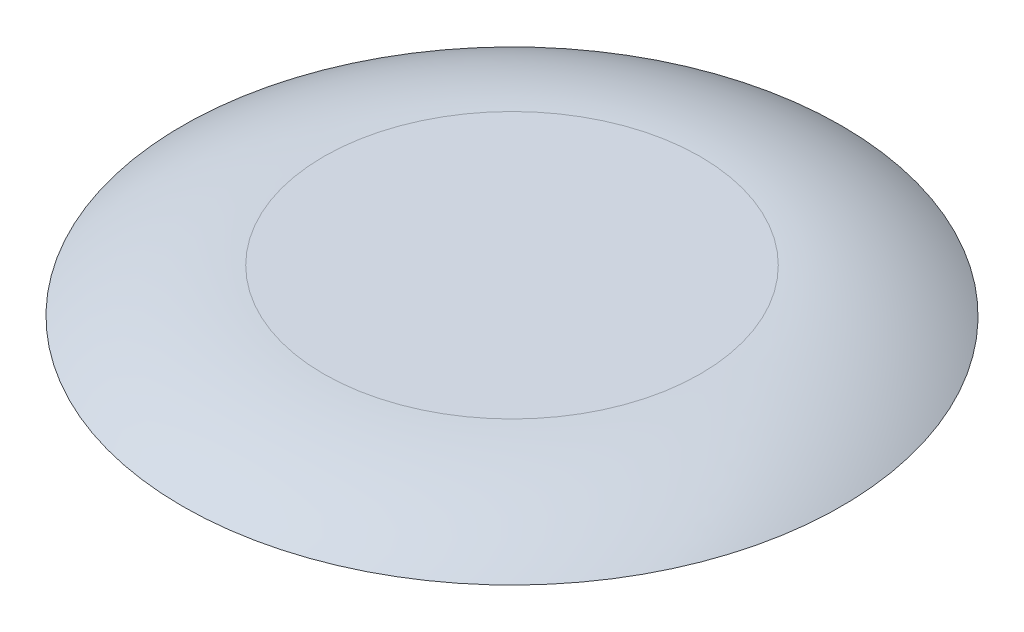
SolidWorks part; units mm, degrees
ref_plane "前视基准面" through (0, 0, 0) normal (0, 0, 1) x (1, 0, 0)
ref_plane "上视基准面" through (0, 0, 0) normal (0, 1, 0) x (1, 0, 0)
ref_plane "右视基准面" through (0, 0, 0) normal (1, 0, 0) x (0, 0, -1)
sketch "草图1" plane through (0, 0, 0) normal (0, 1, 0) x (1, 0, 0)
  circle A0 centre (0, 0) radius 22.5
  dimension "D1" = 45
extrude "凸台-拉伸5" add sketch "草图1" along normal blind 3
fillet "圆角3" radius 17 1 edges at (0, 3, 22.5)
sketch "草图4" plane through (0, 0, 0) normal (0, -1, 0) x (1, 0, 0)
  circle A0 centre (0, 0) radius 22.5
  dimension "D1" = 45
extrude "凸台-拉伸6" add sketch "草图4" along normal blind 3
fillet "圆角4" radius 17 1 edges at (0, -3, -22.5)
